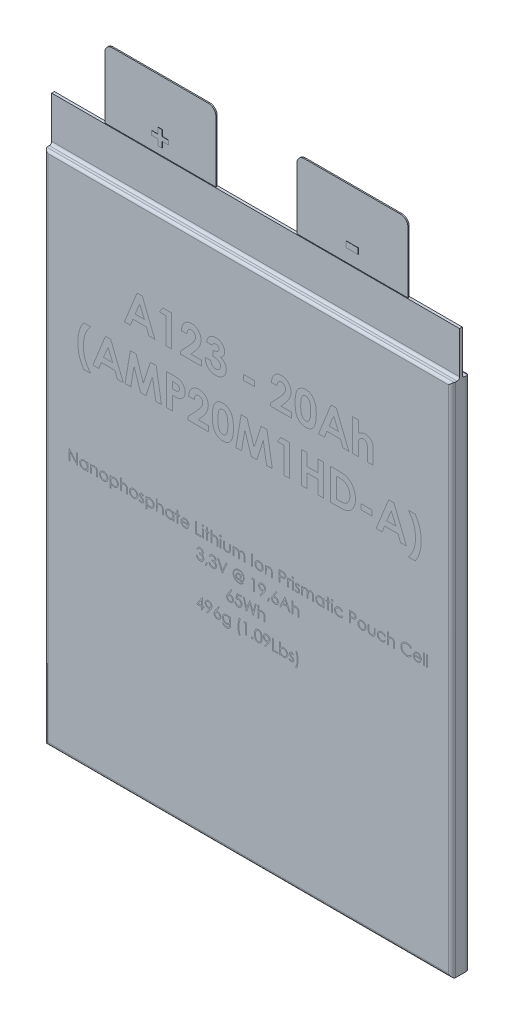
SolidWorks part; units mm, degrees
ref_plane "Face" through (0, 0, 0) normal (0, 0, 1) x (1, 0, 0)
ref_plane "Dessus" through (0, 0, 0) normal (0, 1, 0) x (1, 0, 0)
ref_plane "Droite" through (0, 0, 0) normal (1, 0, 0) x (0, 0, -1)
sketch "Sketch1" plane through (0, 0, 0) normal (0, 0, 1) x (1, 0, 0)
  line L1 (-107.0007, 55.1801) -> (58.9993, 55.1801)
  line L2 (-107.0007, 55.1801) -> (-107.0007, -172.8199)
  line L3 (-107.0007, -172.8199) -> (58.9993, -172.8199)
  line L4 (58.9993, 55.1801) -> (58.9993, -172.8199)
  dimension "D1" = 166
  dimension "D2" = 228
extrude "Boss-Extrude1" add sketch "Sketch1" along normal blind 3.65 and the other way blind 3.65
fillet "Fillet1" radius 1.5 8 edges at (-24.0007, 55.1801, 3.65) (58.9993, -58.8199, 3.65) (-24.0007, -172.8199, 3.65) (-107.0007, -58.8199, 3.65) (-24.0007, -172.8199, -3.65) (58.9993, -58.8199, -3.65) (-24.0007, 55.1801, -3.65) (-107.0007, -58.8199, -3.65)
ref_plane "Mid Plane 1" through (0, 0, 0) normal (0, 0, 1) x (1, 0, 0)
sketch "Sketch2" plane through (0, 0, 0) normal (0, 0, 1) x (1, 0, 0)
  line L0 (-107.0007, 55.1801) -> (58.9993, 55.1801) construction
  line L1 (-24.0007, 55.1801) -> (-24.0007, 65.1801) construction
  line L2 (-7.5007, 65.1801) -> (-7.5007, 55.1801) construction
  line L3 (-40.5007, 55.1801) -> (-85.7007, 55.1801)
  line L4 (-85.7007, 80.1801) -> (-85.7007, 55.1801)
  line L5 (-43.5007, 83.1801) -> (-82.7007, 83.1801)
  line L6 (-40.5007, 80.1801) -> (-40.5007, 55.1801)
  line L7 (-40.5007, 65.1801) -> (-7.5007, 65.1801) construction
  line L8 (-7.5007, 55.1801) -> (37.6993, 55.1801) construction
  line L9 (-4.5007, 83.1801) -> (34.6993, 83.1801) construction
  line L10 (37.6993, 80.1801) -> (37.6993, 55.1801) construction
  line L11 (-7.5007, 80.1801) -> (-7.5007, 55.1801) construction
  arc A0 (-40.5007, 80.1801) -> (-43.5007, 83.1801) centre (-43.5007, 80.1801) ccw
  arc A1 (-82.7007, 83.1801) -> (-85.7007, 80.1801) centre (-82.7007, 80.1801) ccw
  arc A2 (37.6993, 80.1801) -> (34.6993, 83.1801) centre (34.6993, 80.1801) ccw construction
  arc A3 (-4.5007, 83.1801) -> (-7.5007, 80.1801) centre (-4.5007, 80.1801) ccw construction
  point P19 (-40.5007, 83.1801)
  point P22 (-85.7007, 83.1801)
  point P25 (37.6993, 83.1801)
  point P28 (-7.5007, 83.1801)
  point P29 (0, 0)
  point P30 (-24.0007, 65.1801)
  dimension "D4" = 3
  dimension "D5" = 3
  dimension "D1" = 166
  dimension "D2" = 10
  dimension "D3" = 33
  dimension "D6" = 28
  dimension "D7" = 45.2
extrude "Boss-Extrude2" add sketch "Sketch2" along normal blind 0.25 and the other way blind 0.25
ref_plane "Mid Plane 2" through (0, 0, 0) normal (0, 0, 1) x (1, 0, 0)
sketch "Sketch3" plane through (0, 0, 0) normal (0, 0, 1) x (1, 0, 0)
  line L0 (-7.5007, 55.1801) -> (37.6993, 55.1801)
  line L1 (37.6993, 55.1801) -> (37.6993, 80.1801)
  line L2 (34.6993, 83.1801) -> (-4.5007, 83.1801)
  line L3 (-7.5007, 80.1801) -> (-7.5007, 55.1801)
  arc A0 (37.6993, 80.1801) -> (34.6993, 83.1801) centre (34.6993, 80.1801) ccw
  arc A1 (-4.5007, 83.1801) -> (-7.5007, 80.1801) centre (-4.5007, 80.1801) ccw
  point P11 (37.6993, 83.1801)
  point P14 (-7.5007, 83.1801)
  dimension "D1" = 3
extrude "Boss-Extrude3" add sketch "Sketch3" along normal blind 0.25 and the other way blind 0.25
sketch "Sketch7" plane through (0, 0, -3.65) normal (0, 0, -1) x (-1, 0, 0)
  line L0 (107.0007, 55.1801) -> (107.0007, -172.8199) construction
  line L1 (-58.9993, 55.1801) -> (107.0007, 55.1801)
  line L2 (-58.9993, 55.1801) -> (-58.9993, 37.1801)
  line L3 (-58.9993, 37.1801) -> (107.0007, 37.1801)
  line L4 (107.0007, 55.1801) -> (107.0007, 37.1801)
  dimension "D1" = 18
extrude "Cut-Extrude1" cut sketch "Sketch7" against normal blind 3.1
mirror "Mirror2" about plane through (0, 0, 0) normal (0, 0, 1) of "Cut-Extrude1"
ref_plane "Plane3" through (0, 0, 0.25) normal (0, 0, 1) x (1, 0, 0)
sketch "Sketch4" plane through (0, 0, 0.25) normal (0, 0, 1) x (1, 0, 0)
  line L0 (-85.7007, 67.6801) -> (-47.0007, 67.6801) construction
  line L1 (-85.7007, 80.1801) -> (-85.7007, 55.1801) construction
  line L2 (37.6993, 55.1801) -> (37.6993, 80.1801) construction
  line L3 (-7.5007, 56.4788) -> (37.6993, 56.4788) construction
  line L4 (-85.7007, 56.4788) -> (-40.5007, 56.4788) construction
  line L5 (-7.0007, 67.6801) -> (37.6993, 67.6801) construction
  line L6 (-40.5007, 55.1801) -> (-40.5007, 80.1801) construction
  line L7 (-7.5007, 80.1801) -> (-7.5007, 55.1801) construction
  text T0 "+" font "Century Gothic" height 10
  text T1 "-" font "Century Gothic" height 14
  point P8 (0, 0)
  point P9 (-40.5007, 56.1416)
  point P17 (-85.7007, 56.1416)
  point P18 (-7.5007, 56.4788)
  point P21 (37.6993, 56.4788)
extrude "Boss-Extrude4" add sketch "Sketch4" along normal blind 0.1
ref_plane "MidPlane 3" through (0, 0, 0) normal (0, 0, 1) x (1, 0, 0)
mirror "Mirror1" about plane through (0, 0, 0) normal (0, 0, 1) of "Boss-Extrude4"
ref_plane "Plane4" through (0, 0, 8.65) normal (0, 0, 1) x (1, 0, 0)
sketch "Sketch5" plane through (0, 0, 8.65) normal (0, 0, 1) x (1, 0, 0)
  line L0 (-107.0007, -67.8199) -> (58.9993, -67.8199) construction
  line L1 (-107.0007, -172.8199) -> (-107.0007, 37.1801) construction
  line L2 (58.9993, 37.1801) -> (58.9993, -172.8199) construction
  line L3 (-24.0007, 55.1801) -> (-24.0007, -172.8199) construction
  line L5 (58.9993, -172.8199) -> (-107.0007, -172.8199) construction
  line L6 (-105.5007, -7.5199) -> (58.9993, -7.5199) construction
  line L7 (58.9993, 37.1801) -> (58.9993, -172.8199) construction
  line L8 (-105.5007, 37.1801) -> (-105.5007, -171.3199) construction
  text T0 "A123 - 20Ah\r\n(AMP20M1HD-A)" font "Century Gothic" height 12.7
  point P8 (58.9993, -7.5199)
  point P15 (-27.0007, 55.1801)
  point P17 (-105.5007, -7.5199)
wrap "Wrap1" sketch "Sketch5" wrap type scribe source sketch "Sketch5" face at (-24.0007, -67.0699, 3.65)
ref_plane "Plane5" through (0, 0, 13.65) normal (0, 0, 1) x (1, 0, 0)
sketch "Sketch6" plane through (0, 0, 13.65) normal (0, 0, 1) x (1, 0, 0)
  line L0 (-107.0007, -67.8199) -> (58.9993, -67.8199) construction
  text T0 "Nanophosphate Lithium Ion Prismatic Pouch Cell\r\n3,3V @ 19,6Ah\r\n65Wh \r\n496g (1.09Lbs)" font "Century Gothic" height 4.5
wrap "Wrap2" sketch "Sketch6" wrap type scribe source sketch "Sketch6" face at (-24.0007, -67.0699, 3.65)
ref_plane "Plane6" through (0, 0, 0) normal (0, 0, 1) x (1, 0, 0)
ref_plane "Plane7" through (0, -44.8199, 0) normal (0, -1, 0) x (-1, 0, 0)
ref_plane "Plane8" through (-24.0007, 0, 0) normal (-1, 0, 0) x (0, 0, 1)
sketch "bounding_box" plane through (0, 0, 0) normal (0, 0, 1) x (1, 0, 0)
  line L0 (-105.5007, 47.9786) -> (57.4993, 47.9786) construction
  line L5 (-105.5007, 37.1801) -> (-105.5007, -171.3199) construction
  line L6 (57.4993, -171.3199) -> (57.4993, 37.1801) construction
  line L7 (-24.0007, 47.9786) -> (-24.0007, -191.8118) construction
  line L9 (-100.4228, 55.1801) -> (-100.4228, -172.8199) construction
  line L11 (58.9993, -172.8199) -> (-107.0007, -172.8199) construction
  line L12 (-100.1918, -58.8199) -> (83.0974, -58.8199) construction
  line L13 (-86.4007, 55.6801) -> (-86.4007, 84.6801)
  line L14 (59.9993, -173.3199) -> (-108.0007, -173.3199)
  line L15 (59.9993, -173.3199) -> (59.9993, 55.6801)
  line L16 (59.9993, 55.6801) -> (38.3993, 55.6801)
  line L17 (-108.0007, -173.3199) -> (-108.0007, 55.6801)
  line L18 (59.9993, -173.3199) -> (-108.0007, 55.6801) construction
  line L19 (59.9993, 55.6801) -> (-108.0007, -173.3199) construction
  line L20 (-86.4007, 84.6801) -> (-39.9007, 84.6801)
  line L21 (-39.9007, 84.6801) -> (-39.9007, 55.6801)
  line L22 (-8.1007, 55.6801) -> (-8.1007, 84.6801)
  line L23 (-8.1007, 84.6801) -> (38.3993, 84.6801)
  line L24 (38.3993, 84.6801) -> (38.3993, 55.6801)
  line L25 (-86.4007, 55.6801) -> (-108.0007, 55.6801)
  line L26 (-8.1007, 55.6801) -> (-39.9007, 55.6801)
  point P15 (-24.0007, -58.8199)
  point P19 (-24.0007, 47.9786)
  point P20 (-100.4228, -58.8199)
  point P21 (-24.0007, -58.8199)
  point P33 (-24.0007, 55.6801)
  dimension "D1" = 168
  dimension "D2" = 229
  dimension "D3" = 29
  dimension "D4" = 46.5
  dimension "D5" = 31.8
fillet "Fillet2" radius 1 4 edges at (-24.0007, 37.1801, -3.65) (-24.0007, 37.1801, -0.55) (-24.0007, 37.1801, 0.55) (-24.0007, 37.1801, 3.65) tangent propagation no
